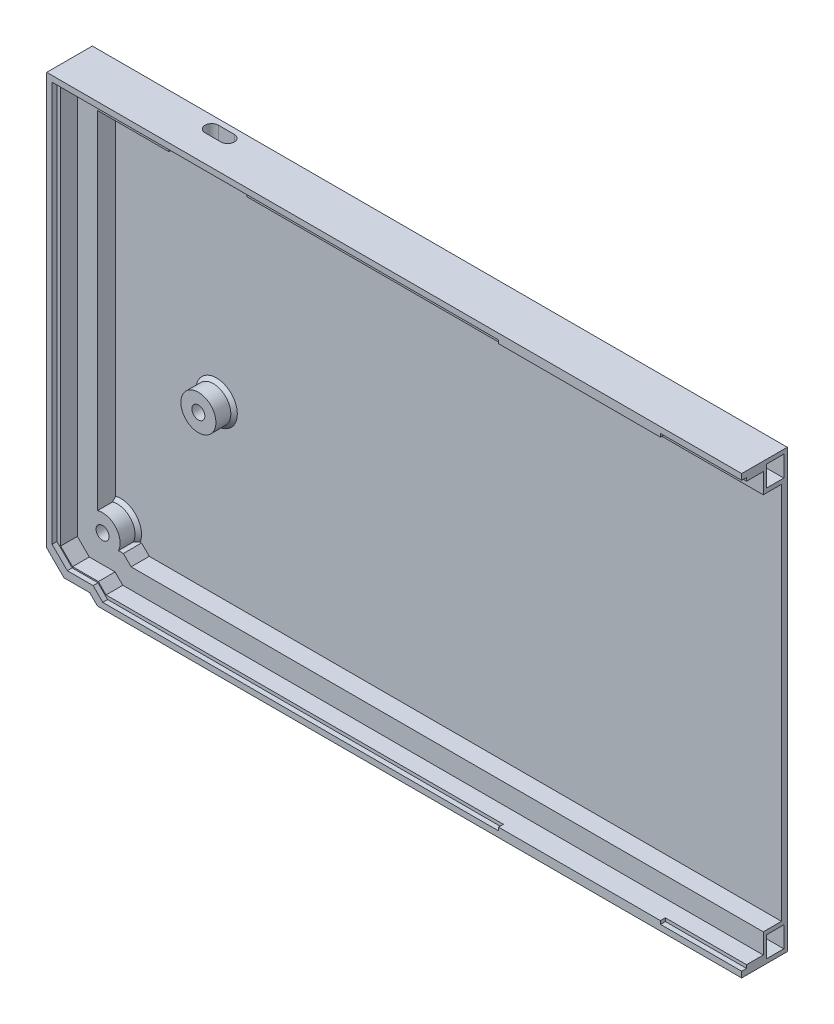
SolidWorks part; units mm, degrees
ref_plane "Přední rovina" through (0, 0, 0) normal (0, 0, 1) x (1, 0, 0)
ref_plane "Horní rovina" through (0, 0, 0) normal (0, 1, 0) x (1, 0, 0)
ref_plane "Pravá rovina" through (0, 0, 0) normal (1, 0, 0) x (0, 0, -1)
sketch "Skica3" plane through (0, 0, 0) normal (0, 0, 1) x (1, 0, 0)
  line L0 (0, 0) -> (415.1053, 0) construction
  line L1 (415.1053, 0) -> (416.6927, -1.5875) construction
  line L2 (416.6927, -1.5875) -> (416.6927, -119.8485) construction
  line L3 (0, 0) -> (-1.5875, -1.5875) construction
  line L4 (-1.5875, -1.5875) -> (-1.5875, -119.8485) construction
  line L5 (-1.5875, -119.8485) -> (0.7934, -122.2292) construction
  line L6 (0.7934, -122.2292) -> (8.7304, -122.2292) construction
  line L7 (8.7304, -122.2292) -> (11.1113, -124.61) construction
  line L8 (11.1113, -124.61) -> (403.9933, -124.61) construction
  line L9 (403.9933, -124.61) -> (406.3744, -122.2294) construction
  line L10 (406.3744, -122.2294) -> (414.3114, -122.2294) construction
  line L11 (416.6927, -119.8485) -> (414.3114, -122.2294) construction
  line L12 (2.4125, -4) -> (412.6927, -4)
  line L13 (412.6927, -4) -> (412.6927, -4)
  line L14 (412.6927, -4) -> (412.6927, -118.1914)
  line L15 (412.6927, -118.1914) -> (412.6547, -118.2294)
  line L16 (404.7177, -118.2294) -> (412.6547, -118.2294)
  line L17 (402.3367, -120.61) -> (404.7177, -118.2294)
  line L18 (12.7681, -120.61) -> (402.3367, -120.61)
  line L19 (10.3872, -118.2292) -> (12.7681, -120.61)
  line L20 (2.4502, -118.2292) -> (10.3872, -118.2292)
  line L21 (2.4125, -118.1915) -> (2.4502, -118.2292)
  line L22 (2.4125, -4) -> (2.4125, -118.1915)
  line L23 (2.4125, -4) -> (2.4125, -4)
  line L24 (-1.5875, -119.8485) -> (415.1053, 0) construction
  line L26 (0, 0) -> (416.6927, -119.8485) construction
  dimension "D1" = 135
  dimension "D2" = 135
  dimension "D3" = 4
  dimension "D4" = 2.245
  dimension "D5" = 2.245
  dimension "D6" = 118.261
  dimension "D7" = 118.261
  dimension "D8" = 3.367
  dimension "D9" = 7.937
  dimension "D10" = 3.367
  dimension "D11" = 392.882
  dimension "D12" = 3.367
  dimension "D13" = 7.937
  dimension "D14" = 3.3674
extrude "Přidat vysunutím1" add sketch "Skica3" along normal blind 5.6
shell "Skořepina1" thickness 1.8 removed face at (207.5525, -95.852, 5.6) outward yes
sketch "Skica7" plane through (0, 0, 5.6) normal (0, 0, 1) x (1, 0, 0)
  line L20 (-6.5875, 5) -> (-6.5875, -121.9196)
  line L21 (-6.5875, -121.9196) -> (-1.2775, -127.2292)
  line L22 (-1.2775, -127.2292) -> (6.6595, -127.2292)
  line L23 (6.6595, -127.2292) -> (9.0403, -129.61)
  line L24 (9.0403, -129.61) -> (406.0641, -129.61)
  line L25 (406.0641, -129.61) -> (408.4452, -127.2294)
  line L26 (408.4452, -127.2294) -> (416.3822, -127.2294)
  line L27 (416.3822, -127.2294) -> (421.6927, -121.9198)
  line L28 (421.6927, -121.9198) -> (421.6927, 5)
  line L29 (421.6927, 5) -> (-6.5875, 5)
  line L30 (-6.5875, 5) -> (-6.5875, -121.9196)
  line L31 (-6.5875, -121.9196) -> (-1.2775, -127.2292)
  line L32 (-1.2775, -127.2292) -> (6.6595, -127.2292)
  line L33 (6.6595, -127.2292) -> (9.0403, -129.61)
  line L34 (9.0403, -129.61) -> (406.0641, -129.61)
  line L35 (406.0641, -129.61) -> (408.4452, -127.2294)
  line L36 (408.4452, -127.2294) -> (416.3822, -127.2294)
  line L37 (416.3822, -127.2294) -> (421.6927, -121.9198)
  line L38 (421.6927, -121.9198) -> (421.6927, 5)
  line L39 (421.6927, 5) -> (-6.5875, 5)
  line L40 (-3.7875, 2.2) -> (-3.7875, -120.7598)
  line L41 (-3.7875, -120.7598) -> (-0.1178, -124.4292)
  line L42 (-0.1178, -124.4292) -> (7.8192, -124.4292)
  line L43 (7.8192, -124.4292) -> (10.2001, -126.81)
  line L44 (10.2001, -126.81) -> (404.9045, -126.81)
  line L45 (404.9045, -126.81) -> (407.2855, -124.4294)
  line L46 (407.2855, -124.4294) -> (415.2225, -124.4294)
  line L47 (415.2225, -124.4294) -> (418.8927, -120.7598)
  line L48 (418.8927, -120.7598) -> (418.8927, 2.2)
  line L49 (418.8927, 2.2) -> (-3.7875, 2.2)
  line L50 (-3.7875, 2.2) -> (-3.7875, -120.7598)
  line L51 (-3.7875, -120.7598) -> (-0.1178, -124.4292)
  line L52 (-0.1178, -124.4292) -> (7.8192, -124.4292)
  line L53 (7.8192, -124.4292) -> (10.2001, -126.81)
  line L54 (10.2001, -126.81) -> (404.9045, -126.81)
  line L55 (404.9045, -126.81) -> (407.2855, -124.4294)
  line L56 (407.2855, -124.4294) -> (415.2225, -124.4294)
  line L57 (415.2225, -124.4294) -> (418.8927, -120.7598)
  line L58 (418.8927, -120.7598) -> (418.8927, 2.2)
  line L59 (418.8927, 2.2) -> (-3.7875, 2.2)
  dimension "D2" = 4.4
  dimension "D1" = 7.2
extrude "Přidat vysunutím3" add sketch "Skica7" along normal blind 5.15 separate body
sketch "Skica8" plane through (0, 0, 5.6) normal (0, 0, -1) x (-1, 0, 0)
  line L0 (-421.6927, 5) -> (6.5875, 5)
  line L1 (6.5875, 5) -> (6.5875, -121.9196)
  line L2 (6.5875, 5) -> (6.5875, -121.9196) construction
  line L3 (6.5875, -121.9196) -> (1.2775, -127.2292)
  line L4 (1.2775, -127.2292) -> (-6.6595, -127.2292)
  line L5 (-6.6595, -127.2292) -> (-9.0403, -129.61)
  line L6 (-9.0403, -129.61) -> (-406.0641, -129.61)
  line L7 (-406.0641, -129.61) -> (-408.4452, -127.2294)
  line L8 (-408.4452, -127.2294) -> (-416.3822, -127.2294)
  line L9 (-416.3822, -127.2294) -> (-421.6927, -121.9198)
  line L10 (-421.6927, -121.9198) -> (-421.6927, 5)
  line L11 (-0.6125, -2.2) -> (-0.6125, -118.9371)
  line L12 (-414.4927, -2.2) -> (-0.6125, -2.2) construction
  line L13 (-0.6125, -2.2) -> (-0.6125, -118.9371) construction
  line L14 (-0.6125, -118.9371) -> (-1.7047, -120.0292)
  line L15 (-1.7047, -120.0292) -> (-9.6417, -120.0292)
  line L16 (-9.6417, -120.0292) -> (-12.0226, -122.41)
  line L17 (-12.0226, -122.41) -> (-403.0822, -122.41)
  line L18 (-403.0822, -122.41) -> (-405.4632, -120.0294)
  line L19 (-405.4632, -120.0294) -> (-413.4002, -120.0294) construction
  line L20 (-405.4632, -120.0294) -> (-413.4002, -120.0294)
  line L21 (-413.4002, -120.0294) -> (-414.4927, -118.9371) construction
  line L22 (-413.4002, -120.0294) -> (-414.4927, -118.9371)
  line L23 (-414.4927, -118.9371) -> (-414.4927, -2.2)
  line L24 (-414.4927, -2.2) -> (-0.6125, -2.2)
extrude "Přidat vysunutím4" add sketch "Skica8" along normal up to surface (7.4 mm away) up to face at (207.5525, -96.7211, -1.8)
sketch "Skica11" plane through (0, 0, 10.75) normal (0, 0, 1) x (1, 0, 0)
  line L0 (207.5526, 3.195) -> (207.5526, 5) construction
  line L1 (421.6927, 5) -> (-6.5875, 5) construction
  line L2 (207.5522, -127.805) -> (207.5522, -129.61) construction
  line L3 (9.0403, -129.61) -> (406.0641, -129.61) construction
  line L4 (-4.9474, -58.4598) -> (-6.5875, -58.4598) construction
  line L5 (-6.5875, 5) -> (-6.5875, -121.9196) construction
  line L6 (420.0526, -58.4599) -> (421.6927, -58.4599) construction
  line L7 (421.6927, -121.9198) -> (421.6927, 5) construction
  line L8 (404.9045, -126.81) -> (407.2855, -124.4294) construction
  line L9 (415.2225, -124.4294) -> (418.8927, -120.7598) construction
  line L10 (7.8192, -124.4292) -> (10.2001, -126.81) construction
  line L11 (-3.7875, -120.7598) -> (-0.1178, -124.4292) construction
  line L13 (407.2855, -124.4294) -> (415.2225, -124.4294) construction
  line L14 (-0.1178, -124.4292) -> (7.8192, -124.4292) construction
  line L30 (420.0526, 3.195) -> (-4.9474, 3.195)
  line L31 (-4.9474, 3.195) -> (-4.9474, -120.1146)
  line L32 (-4.9474, -120.1146) -> (-0.24, -124.8217)
  line L33 (-0.24, -124.8217) -> (7.697, -124.8217)
  line L34 (7.697, -124.8217) -> (10.6804, -127.805)
  line L35 (10.6804, -127.805) -> (404.4241, -127.805)
  line L36 (404.4241, -127.805) -> (406.8051, -125.4244)
  line L37 (406.8051, -125.4244) -> (414.7421, -125.4244)
  line L38 (414.7421, -125.4244) -> (420.0526, -120.1148)
  line L39 (420.0526, -120.1148) -> (420.0526, 3.195)
  line L45 (421.6927, 5) -> (-6.5875, 5)
  line L46 (-6.5875, 5) -> (-6.5875, -121.9196)
  line L47 (-6.5875, -121.9196) -> (-1.2775, -127.2292)
  line L48 (-1.2775, -127.2292) -> (6.6595, -127.2292)
  line L49 (6.6595, -127.2292) -> (9.0403, -129.61)
  line L50 (9.0403, -129.61) -> (406.0641, -129.61)
  line L51 (406.0641, -129.61) -> (408.4452, -127.2294)
  line L52 (408.4452, -127.2294) -> (416.3822, -127.2294)
  line L53 (416.3822, -127.2294) -> (421.6927, -121.9198)
  line L54 (421.6927, -121.9198) -> (421.6927, 5)
  line L55 (421.6927, 5) -> (-6.5875, 5)
  line L56 (-6.5875, 5) -> (-6.5875, -121.9196)
  line L57 (-6.5875, -121.9196) -> (-1.2775, -127.2292)
  line L58 (-1.2775, -127.2292) -> (6.6595, -127.2292)
  line L59 (6.6595, -127.2292) -> (9.0403, -129.61)
  line L60 (9.0403, -129.61) -> (406.0641, -129.61)
  line L61 (406.0641, -129.61) -> (408.4452, -127.2294)
  line L62 (408.4452, -127.2294) -> (416.3822, -127.2294)
  line L63 (416.3822, -127.2294) -> (421.6927, -121.9198)
  line L64 (421.6927, -121.9198) -> (421.6927, 5)
  point P0 (207.5523, -63.11)
  point P2 (207.5523, -63.11)
  dimension "D1" = 131
  dimension "D2" = 425
  dimension "D3" = 0
extrude "Přidat vysunutím5" add sketch "Skica11" along normal blind 1.5
sketch "Skica14" plane through (0, 0, 10.75) normal (0, 0, 1) x (1, 0, 0)
  line L0 (418.8927, 2.2) -> (-3.7875, 2.2) construction
  line L1 (182.5326, 2.2) -> (132.6326, 2.2)
  line L2 (182.5326, 2.2) -> (182.5326, 3.195)
  line L3 (182.5326, 3.195) -> (132.6326, 3.195)
  line L4 (132.6326, 2.2) -> (132.6326, 3.195)
  line L5 (420.0526, 3.195) -> (-4.9474, 3.195) construction
  line L6 (418.8927, 2.2) -> (-3.7875, 2.2) construction
  line L7 (232.5726, 2.2) -> (282.4726, 2.2)
  line L8 (232.5726, 2.2) -> (232.5726, 3.195)
  line L9 (232.5726, 3.195) -> (282.4726, 3.195)
  line L10 (282.4726, 2.2) -> (282.4726, 3.195)
  line L11 (207.5526, 3.195) -> (207.5522, -127.805) construction
  line L12 (10.6804, -127.805) -> (404.4241, -127.805) construction
  line L13 (10.2001, -126.81) -> (404.9045, -126.81) construction
  line L14 (232.5722, -126.81) -> (282.4722, -126.81)
  line L15 (232.5722, -126.81) -> (232.5722, -127.805)
  line L16 (232.5722, -127.805) -> (282.4722, -127.805)
  line L17 (282.4722, -126.81) -> (282.4722, -127.805)
  line L18 (10.6804, -127.805) -> (404.4241, -127.805) construction
  line L20 (182.5322, -126.81) -> (132.6322, -126.81)
  line L21 (182.5322, -126.81) -> (182.5322, -127.805)
  line L22 (182.5322, -127.805) -> (132.6322, -127.805)
  line L23 (132.6322, -126.81) -> (132.6322, -127.805)
  dimension "D1" = 49.9
  dimension "D2" = 49.9
  dimension "D3" = 25.02
  dimension "D4" = 25.02
  dimension "D5" = 49.9
  dimension "D6" = 49.9
  dimension "D7" = 25.02
  dimension "D8" = 25.02
extrude "Přidat vysunutím6" add sketch "Skica14" along normal up to surface (1.5 mm away) up to face at (207.5524, -100.1977, 12.25)
sketch "Skica15" plane through (0, 0, 0) normal (0, 0, 1) x (1, 0, 0)
  line L1 (34.9015, 4.5) -> (37.9015, 4.5)
  line L2 (34.9015, 4.5) -> (34.9015, -4.5)
  line L3 (34.9015, -4.5) -> (37.9015, -4.5)
  line L4 (37.9015, 4.5) -> (37.9015, -4.5)
  line L5 (34.9015, 4.5) -> (37.9015, -4.5) construction
  line L6 (34.9015, -4.5) -> (37.9015, 4.5) construction
  line L20 (-1.5875, 0) -> (-1.5875, -119.8485)
  line L21 (-1.5875, -119.8485) -> (0.7934, -122.2292)
  line L22 (0.7934, -122.2292) -> (8.7304, -122.2292)
  line L23 (8.7304, -122.2292) -> (11.1113, -124.61)
  line L24 (11.1113, -124.61) -> (403.9933, -124.61)
  line L25 (403.9933, -124.61) -> (406.3744, -122.2294)
  line L26 (406.3744, -122.2294) -> (414.3114, -122.2294)
  line L27 (414.3114, -122.2294) -> (416.6927, -119.8485)
  line L28 (416.6927, -119.8485) -> (416.6927, 0)
  line L29 (416.6927, 0) -> (-1.5875, 0)
  line L30 (-1.5875, 0) -> (-1.5875, -119.8485) construction
  line L31 (-1.5875, -119.8485) -> (0.7934, -122.2292) construction
  line L32 (0.7934, -122.2292) -> (8.7304, -122.2292) construction
  line L33 (8.7304, -122.2292) -> (11.1113, -124.61) construction
  line L34 (11.1113, -124.61) -> (403.9933, -124.61) construction
  line L35 (403.9933, -124.61) -> (406.3744, -122.2294) construction
  line L36 (406.3744, -122.2294) -> (414.3114, -122.2294) construction
  line L37 (414.3114, -122.2294) -> (416.6927, -119.8485) construction
  line L38 (416.6927, -119.8485) -> (416.6927, 0) construction
  line L39 (416.6927, 0) -> (-1.5875, 0) construction
  circle A0 centre (3.9685, -115.9542) radius 5.4
  circle A1 centre (33.4915, -69.051) radius 5.4
  circle A2 centre (411.1977, -115.8794) radius 5.4
  circle A3 centre (334.1477, -53.972) radius 5.4
  point P2 (-1.4315, -115.9542)
  point P3 (3.9685, -121.3542)
  point P4 (28.0915, -69.051)
  point P8 (33.4915, -74.451)
  point P12 (411.1977, -121.2794)
  point P13 (416.5977, -115.8794)
  point P17 (334.1477, -48.572)
  point P19 (339.5477, -53.972)
  point P21 (36.4015, 0)
  point P23 (36.4015, 0)
  dimension "D2" = 0.156
  dimension "D4" = 10.8
  dimension "D7" = 10.8
  dimension "D10" = 10.8
  dimension "D13" = 10.8
  dimension "D3" = 0.875
  dimension "D5" = 29.679
  dimension "D6" = 50.159
  dimension "D8" = 0.095
  dimension "D9" = 0.95
  dimension "D11" = 77.145
  dimension "D12" = 48.572
  dimension "D14" = 37.989
  dimension "D15" = 9
  dimension "D16" = 3
  dimension "D1" = 4
extrude "Přidat vysunutím7" add sketch "Skica15" along normal blind 5.6
sketch "Skica16" plane through (0, 0, 5.6) normal (0, 0, 1) x (1, 0, 0)
  circle A0 centre (3.9685, -115.9542) radius 2
  circle A1 centre (33.4915, -69.051) radius 2
  circle A2 centre (334.1477, -53.972) radius 2
  circle A3 centre (411.1977, -115.8794) radius 2
  dimension "D1" = 4
  dimension "D2" = 4
  dimension "D3" = 4
  dimension "D4" = 4
extrude "Odebrat vysunutím1" cut sketch "Skica16" against normal blind 5.75
chamfer "Zkosení1" distance 1 angle 45 4 edges at (407.0694, -112.3984, 0) (8.0492, -112.4175, 0) (38.8915, -69.051, 0) (339.5477, -53.972, 0)
sketch "Skica17" plane through (0, 0, 5.6) normal (0, 0, 1) x (1, 0, 0)
  line L0 (34.9015, -4.5) -> (37.9015, -4.5) construction
  line L1 (24.4015, -11.2) -> (48.4015, -11.2)
  line L2 (24.4015, -11.2) -> (24.4015, 2.2)
  line L3 (24.4015, 2.2) -> (48.4015, 2.2)
  line L4 (48.4015, -11.2) -> (48.4015, 2.2)
  line L5 (24.4015, -11.2) -> (48.4015, 2.2) construction
  line L6 (24.4015, 2.2) -> (48.4015, -11.2) construction
  line L7 (418.8927, 2.2) -> (-3.7875, 2.2) construction
  point P0 (36.4015, -4.5)
  dimension "D1" = 24
extrude "Odebrat vysunutím2" cut sketch "Skica17" against normal blind 1.6
sketch "Skica18" plane through (0, -4.5, 0) normal (0, -1, 0) x (1, 0, 0)
  line L0 (33.9515, 1.95) -> (38.8515, 1.95) construction
  line L1 (36.4015, 4) -> (36.4015, 1.95) construction
  line L2 (37.9015, 4) -> (34.9015, 4) construction
  line L3 (33.9515, 4) -> (38.8515, 4)
  line L4 (33.9515, -0.1) -> (38.8515, -0.1)
  arc A0 (33.9515, 4) -> (33.9515, -0.1) centre (33.9515, 1.95) ccw
  arc A1 (38.8515, -0.1) -> (38.8515, 4) centre (38.8515, 1.95) ccw
  point P6 (36.4015, 1.95)
  point P11 (31.9015, 1.95)
  point P12 (40.9015, 1.95)
  dimension "D1" = 9
  dimension "D3" = 2.05
  dimension "D2" = 4.1
extrude "Odebrat vysunutím3" cut sketch "Skica18" against normal up to surface (9.5 mm away) up to face at (207.5526, 5, 5.225)
sketch "Skica23" plane through (-6.5875, 0, 0) normal (-1, 0, 0) x (0, 0, 1)
  line L2 (-1.8, 5) -> (-1.8, -121.9196) construction
  line L4 (-1.8, -58.4598) -> (12.25, -58.4598) construction
  line L5 (12.25, 5) -> (12.25, -121.9196) construction
  circle A0 centre (3.2, -18.4598) radius 2
  circle A1 centre (3.2, -98.4598) radius 2
  point P8 (-1.8, -58.4598)
  dimension "D2" = 4
  dimension "D3" = 4
  dimension "D1" = 40
  dimension "D4" = 5
extrude "Odebrat vysunutím4" cut sketch "Skica23" against normal blind 5.7
sketch "Skica24" plane through (421.6927, 0, 0) normal (1, 0, 0) x (0, 0, -1)
  line L0 (1.8, -58.4599) -> (-12.25, -58.4599) construction
  line L1 (1.8, -121.9198) -> (1.8, 5) construction
  line L2 (-12.25, -121.9198) -> (-12.25, 5) construction
  circle A0 centre (-3.2, -18.4599) radius 2
  circle A1 centre (-3.2, -98.4599) radius 2
  dimension "D1" = 4
  dimension "D2" = 4
  dimension "D3" = 40
  dimension "D4" = 5
extrude "Odebrat vysunutím5" cut sketch "Skica24" against normal blind 5.7
sketch "Skica25" plane through (0, 0, -1.8) normal (0, 0, -1) x (-1, 0, 0)
  line L0 (-421.6927, -121.9198) -> (-421.6927, 5) construction
  line L1 (-421.6927, 5) -> (6.5875, 5) construction
  line L2 (6.5875, 5) -> (6.5875, -121.9196) construction
  line L3 (-9.0403, -129.61) -> (-406.0641, -129.61) construction
  circle A0 centre (-401.6927, -15) radius 6.25
  circle A1 centre (-13.4125, -15) radius 6.25
  circle A2 centre (-388.4452, -109.61) radius 6.25
  circle A3 centre (-26.6595, -109.61) radius 6.25
  dimension "D1" = 12.5
  dimension "D2" = 12.5
  dimension "D3" = 12.5
  dimension "D4" = 12.5
  dimension "D5" = 20
  dimension "D6" = 20
  dimension "D7" = 20
  dimension "D8" = 20
  dimension "D9" = 20
  dimension "D10" = 20
  dimension "D11" = 20
  dimension "D12" = 20
extrude "Odebrat vysunutím6" cut sketch "Skica25" against normal blind 1.5
sketch "Skica26" plane through (0, 5, 0) normal (0, 1, 0) x (1, 0, 0)
  line L0 (207.5526, 1.8) -> (207.5526, -12.25)
  line L1 (421.6927, 1.8) -> (-6.5875, 1.8) construction
  line L2 (421.6927, -12.25) -> (-6.5875, -12.25) construction
  line L3 (207.5526, -12.25) -> (421.6927, -12.25)
  line L4 (421.6927, -12.25) -> (421.6927, 1.8)
  line L5 (421.6927, 1.8) -> (207.5526, 1.8)
extrude "Odebrat vysunutím7" cut sketch "Skica26" against normal through all
sketch "Skica27" plane through (207.5526, 0, 0) normal (1, 0, 0) x (0, 0, -1)
  line L0 (0, -4) -> (1.8, -4) construction
  line L1 (1.8, -129.61) -> (1.8, 5) construction
  line L2 (-5.6, 2.2) -> (-5.6, 5) construction
  line L3 (1.8, 5) -> (-12.25, 5) construction
  line L4 (0, -120.61) -> (1.8, -120.61) construction
  line L5 (-5.6, -126.81) -> (-5.6, -129.61) construction
  line L6 (1.8, -129.61) -> (-12.25, -129.61) construction
  line L7 (-5.6, -129.61) -> (1.8, -120.61) construction
  line L8 (-5.6, -120.61) -> (1.8, -129.61) construction
  line L9 (-5.6, -4) -> (1.8, 5) construction
  line L10 (-5.6, 5) -> (1.8, -4) construction
  line L11 (0, -120.61) -> (-5.6, -120.61) construction
  line L12 (-4.5311, -2.7) -> (0.7311, -2.7)
  line L13 (-4.5311, -2.7) -> (-4.5311, 3.7)
  line L14 (-4.5311, 3.7) -> (0.7311, 3.7)
  line L15 (0.7311, -2.7) -> (0.7311, 3.7)
  line L16 (-4.5311, -2.7) -> (0.7311, 3.7) construction
  line L17 (-4.5311, 3.7) -> (0.7311, -2.7) construction
  line L18 (-4.5311, -128.31) -> (0.7311, -128.31)
  line L19 (-4.5311, -128.31) -> (-4.5311, -121.91)
  line L20 (-4.5311, -121.91) -> (0.7311, -121.91)
  line L21 (0.7311, -128.31) -> (0.7311, -121.91)
  line L22 (-4.5311, -128.31) -> (0.7311, -121.91) construction
  line L23 (-4.5311, -121.91) -> (0.7311, -128.31) construction
  point P25 (-1.9, 0.5)
  point P30 (-1.9, -125.11)
  dimension "D1" = 1.3
  dimension "D2" = 1.3
extrude "Odebrat vysunutím8" cut sketch "Skica27" against normal blind 17
